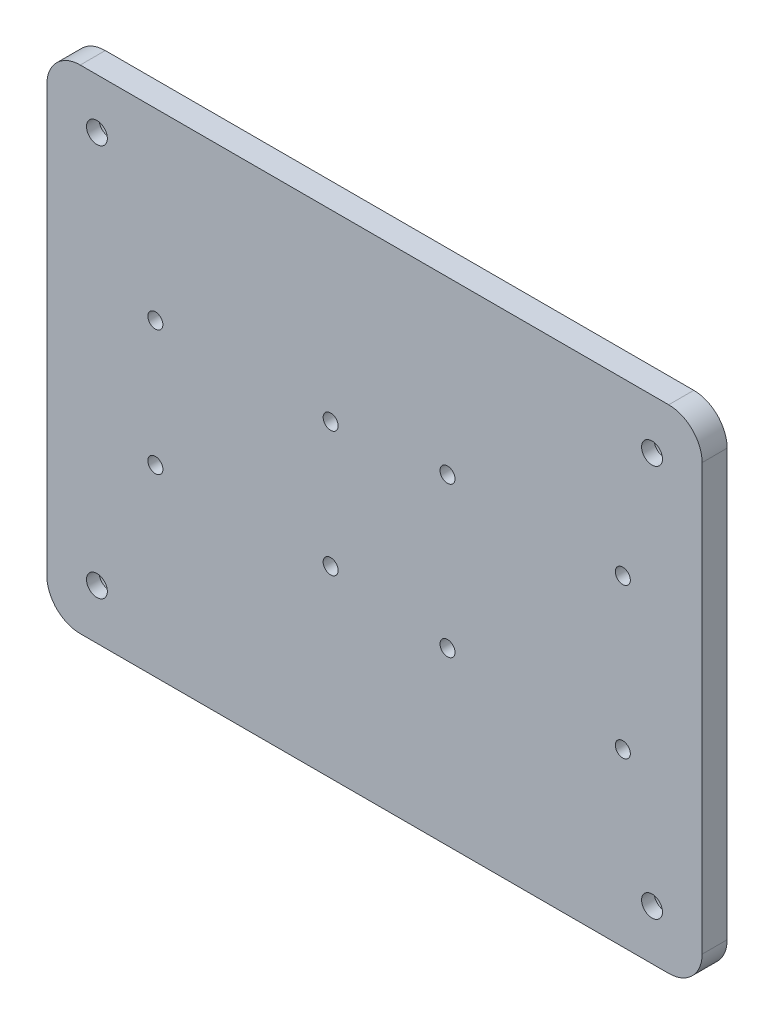
SolidWorks part; units mm, degrees
ref_plane "前视基准面" through (0, 0, 0) normal (0, 0, 1) x (1, 0, 0)
ref_plane "上视基准面" through (0, 0, 0) normal (0, 1, 0) x (1, 0, 0)
ref_plane "右视基准面" through (0, 0, 0) normal (1, 0, 0) x (0, 0, -1)
other "Configuration Table"
sketch "草图2" plane through (0, 0, 0) normal (0, 1, 0) x (1, 0, 0)
  line L9 (0, 0) -> (170, 0)
  line L10 (0, 0) -> (0, -20)
  line L11 (0, -20) -> (170, -20)
  line L12 (170, 0) -> (170, -20)
  dimension "D1" = 170
  dimension "D2" = 20
extrude "凸台-拉伸1" add sketch "草图2" along normal blind 23
sketch "草图3" plane through (0, 23, 0) normal (0, 1, 0) x (1, 0, 0)
  line L0 (123.9417, -11.2) -> (126.0583, -11.2)
  line L1 (158.9417, -11.2) -> (161.0583, -11.2)
  line L2 (0, -20) -> (170, -20) construction
  line L3 (170, -20) -> (170, 0) construction
  circle A0 centre (125, -10) radius 1.6
  circle A1 centre (160, -10) radius 1.6
  dimension "D1" = 3.2
  dimension "D2" = 10
  dimension "D3" = 45
  dimension "D4" = 10
  dimension "D5" = 10
  dimension "D6" = 1.2
extrude "切除-拉伸1" cut sketch "草图3" against normal through all contours L1 A1 | L0 A0 region at (125, 23, 9.8941) region at (160, 23, 9.8941)
sketch "草图4" plane through (170, 0, 0) normal (1, 0, 0) x (0, 0, -1)
  line L0 (0, 23) -> (0, 0) construction
  line L1 (0, 18) -> (-17, 18)
  line L2 (0, 18) -> (0, 5)
  line L3 (0, 5) -> (-17, 5)
  line L4 (-17, 18) -> (-17, 5)
  line L5 (-17, 18) -> (-17, 23)
  line L6 (-20, 23) -> (0, 23) construction
  line L7 (-17, 5) -> (-17, 0)
  line L8 (-20, 0) -> (0, 0) construction
  line L9 (-20, 23) -> (-20, 0) construction
  line M6 (0, 0) -> (0, 23)
  dimension "D1" = 13
  dimension "D2" = 3
extrude "切除-拉伸2" cut sketch "草图4" against normal blind 30 contours L1 L4 L3 M6 region at (170, 11.5, 8.5)
sketch "草图5" plane through (0, 23, 0) normal (0, 1, 0) x (1, 0, 0)
  line L0 (117.5, -10) -> (117.5, -20)
  line L1 (0, -20) -> (170, -20) construction
  line L2 (132.5, -10) -> (132.5, -20)
  line L3 (152.5, -10) -> (152.5, -20)
  line L4 (167.5, -10) -> (167.5, -20)
  line L5 (132.5, -17) -> (152.5, -17)
  line L6 (167.5, -17) -> (170, -17)
  line L7 (170, -20) -> (170, 0) construction
  line L8 (132.5, -17) -> (102.5, -17)
  line L9 (102.5, -17) -> (102.5, 0)
  line L10 (170, 0) -> (0, 0) construction
  line L11 (102.5, -17) -> (102.5, -20)
  circle A0 centre (125, -10) radius 7.5
  circle A1 centre (160, -10) radius 7.5
  arc A2 (126.0583, -11.2) -> (123.9417, -11.2) centre (125, -10) ccw construction
  arc A3 (161.0583, -11.2) -> (158.9417, -11.2) centre (160, -10) ccw construction
  line M10 (0, 0) -> (0, -20)
  line M11 (0, -20) -> (170, -20)
  line M12 (170, -20) -> (170, 0)
  line M13 (170, 0) -> (0, 0)
  dimension "D1" = 15
  dimension "D2" = 3
  dimension "D3" = 30
extrude "切除-拉伸3" cut sketch "草图5" against normal through all contours L8 L9 L0 M13 M10 M11 | A1 L4 L6 L9 L8 L0 A0 L2 L5 L3 M12 M13 region at (133.0731, 23, 7.5108) region at (51.25, 23, 10)
sketch "草图6" plane through (0, 0, 20) normal (0, 0, 1) x (1, 0, 0)
  line L1 (92.5, 43) -> (180, 43)
  line L2 (92.5, 43) -> (92.5, -20)
  line L3 (92.5, -20) -> (180, -20)
  line L4 (180, 43) -> (180, -20)
  line L5 (102.5, 23) -> (170, 23) construction
  line L6 (136.25, 43) -> (136.25, 23) construction
  line L7 (136.25, 0) -> (136.25, -20) construction
  line L8 (102.5, 0) -> (170, 0) construction
  line L9 (170, 23) -> (170, 0) construction
  dimension "D1" = 20
  dimension "D2" = 10
extrude "凸台-拉伸2" add sketch "草图6" against normal up to surface (3 mm away) up to face at (110, 11.5, 17)
sketch "草图7" plane through (0, 0, 17) normal (0, 0, -1) x (-1, 0, 0)
  line L0 (-180, -20) -> (-180, 43) construction
  line L1 (-180, 43) -> (-92.5, 43) construction
  line L2 (-92.5, 43) -> (-92.5, -20) construction
  line L3 (-92.5, -20) -> (-180, -20) construction
  circle A0 centre (-174, 35) radius 2
  circle A1 centre (-107.5, 35) radius 2
  circle A2 centre (-174, -12) radius 2
  circle A3 centre (-107.5, -12) radius 2
  circle A4 centre (-174, 35) radius 1.25
  circle A5 centre (-107.5, 35) radius 1.25
  circle A6 centre (-107.5, -12) radius 1.25
  circle A7 centre (-174, -12) radius 1.25
  dimension "D1" = 4
  dimension "D2" = 2.5
  dimension "D3" = 6
  dimension "D4" = 8
  dimension "D5" = 15
  dimension "D6" = 8
extrude "切除-拉伸4" cut sketch "草图7" against normal through all contours A7 | A6 | A5 | A4
extrude "切除-拉伸5" cut sketch "草图7<3>" against normal offset from surface (1.5 mm away) 1.5 contours A2 | A3 | A1 | A0 up to face at (172.75, 35, 20)
sketch "草图7<3>" plane through (0, 0, 17) normal (0, 0, -1) x (-1, 0, 0) same geometry as "草图7"
sketch "草图8" plane through (0, 0, 17) normal (0, 0, -1) x (-1, 0, 0)
  line L0 (-180, 41) -> (-101.5, 41)
  line L1 (-180, -20) -> (-180, 43) construction
  line L2 (-101.5, 41) -> (-101.5, -18)
  line L3 (-101.5, -18) -> (-180, -18)
  line L4 (-180, 43) -> (-92.5, 43) construction
  line L5 (-92.5, -20) -> (-180, -20) construction
  line L6 (-92.5, 43) -> (-92.5, -20) construction
  line L7 (-180, 41) -> (-180, -18)
  line M20 (-92.5, -20) -> (-92.5, 43)
  line M21 (-92.5, 43) -> (-180, 43)
  line M22 (-180, 43) -> (-180, -20)
  line M23 (-180, -20) -> (-92.5, -20)
  dimension "D1" = 2
  dimension "D2" = 2
  dimension "D3" = 9
extrude "切除-拉伸6" cut sketch "草图8" against normal through all contours L2 L3 L0 M22 M23 M20 M21 region at (178.9218, 42, 17)
fillet "圆角2" radius 4 4 edges at (101.5, -18, 18.5) (101.5, 41, 18.5) (180, 41, 18.5) (180, -18, 18.5)
sketch "草图9" plane through (0, -18, 0) normal (0, -1, 0) x (1, 0, 0)
  line L0 (180, 20) -> (180, 17) construction
  line L1 (101.5, 17) -> (180, 17)
  line L2 (101.5, 17) -> (101.5, 0.7915)
  line L3 (101.5, 0.7915) -> (180, 0.7915)
  line L4 (180, 17) -> (180, 0.7915)
sketch "草图10" plane through (0, 0, 17) normal (0, 0, -1) x (-1, 0, 0)
  circle A0 centre (-170.5, 20.5) radius 0.9
  circle A1 centre (-149.5, 20.5) radius 0.9
  circle A2 centre (-170.5, 2.5) radius 0.9
  circle A3 centre (-149.5, 2.5) radius 0.9
  circle A4 centre (-135.5, 4) radius 0.9
  circle A5 centre (-135.5, 19) radius 0.9
  circle A6 centre (-114.5, 19) radius 0.9
  circle A7 centre (-114.5, 4) radius 0.9
  point P16 (0, 0)
  dimension "D1" = 1.8
extrude "切除-拉伸7" cut sketch "草图10" against normal through all
extrude "切除-拉伸8" cut sketch "草图9" against normal through all
